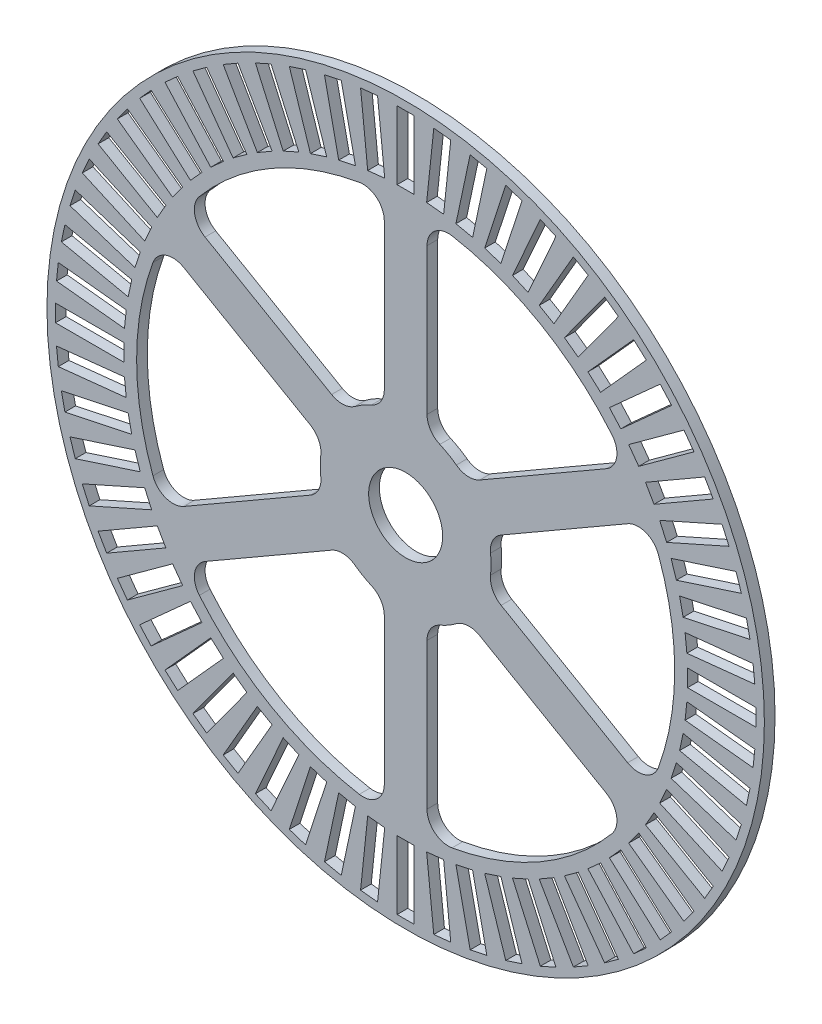
SolidWorks part; units mm, degrees
material "1023 Carbon Steel Sheet (SS)"
ref_plane "Front Plane" through (0, 0, 0) normal (0, 0, 1) x (1, 0, 0)
ref_plane "Top Plane" through (0, 0, 0) normal (0, 1, 0) x (1, 0, 0)
ref_plane "Right Plane" through (0, 0, 0) normal (1, 0, 0) x (0, 0, -1)
sketch "Sketch1" plane through (0, 0, 0) normal (0, 0, 1) x (1, 0, 0)
  circle A0 centre (0, 0) radius 40.005
  circle A1 centre (0, 0) radius 53.34
  dimension "D1" = 106.68
  dimension "D2" = 13.335
extrude "Boss-Extrude1" add sketch "Sketch1" along normal blind 1.5875
sketch "Sketch4" plane through (0, 0, 1.5875) normal (0, 0, 1) x (1, 0, 0)
  line L1 (-1.27, 52.07) -> (1.27, 52.07)
  line L2 (-1.27, 52.07) -> (-1.27, 41.91)
  line L3 (-1.27, 41.91) -> (1.27, 41.91)
  line L4 (1.27, 52.07) -> (1.27, 41.91)
  line L5 (-1.27, 52.07) -> (1.27, 41.91) construction
  line L6 (-1.27, 41.91) -> (1.27, 52.07) construction
  point P0 (0, 46.99)
  dimension "D1" = 2.54
  dimension "D2" = 10.16
  dimension "D3" = 46.99
extrude "Cut-Extrude3" cut sketch "Sketch4" against normal blind 5.08 contours L1 L4 L3 L2
pattern_circular "CirPattern2" count 60 over 360 of "Cut-Extrude3"
sketch "Sketch7" plane through (0, 0, 0) normal (0, 0, -1) x (-1, 0, 0)
  line L0 (-1.905, 0) -> (49998.095, 0) construction
  circle A2 centre (60.325, 0) radius 6.985
  point P6 (60.325, 0)
  dimension "D1" = 60.325
  dimension "D2" = 13.97
extrude "Cut-Extrude5" [suppressed] cut sketch "Sketch7" against normal blind 2.54
pattern_circular "CirPattern4" [suppressed] count 6 over 360 of bodies 110
sketch "Sketch8" plane through (0, 0, 0) normal (0, 0, 1) x (1, 0, 0)
  line L0 (-3.175, 12.2967) -> (-3.175, 39.8788)
  line L1 (3.175, 12.2967) -> (3.175, 39.8788)
  line L2 (9.0618, 8.898) -> (32.9486, 22.689)
  line L3 (12.2368, 3.3987) -> (36.1236, 17.1898)
  line L4 (12.2368, -3.3987) -> (36.1236, -17.1898)
  line L5 (9.0618, -8.898) -> (32.9486, -22.689)
  line L6 (3.175, -12.2967) -> (3.175, -39.8788)
  line L7 (-3.175, -12.2967) -> (-3.175, -39.8788)
  line L8 (-9.0618, -8.898) -> (-32.9486, -22.689)
  line L9 (-12.2368, -3.3987) -> (-36.1236, -17.1898)
  line L10 (-12.2368, 3.3987) -> (-36.1236, 17.1898)
  line L11 (-9.0618, 8.898) -> (-32.9486, 22.689)
  circle A1 centre (0, 0) radius 40.005 construction
  arc A2 (-32.9486, 22.689) -> (-36.1236, 17.1898) centre (0, 0) ccw
  arc A3 (-36.1236, -17.1898) -> (-32.9486, -22.689) centre (0, 0) ccw
  arc A4 (-3.175, -39.8788) -> (3.175, -39.8788) centre (0, 0) ccw
  arc A5 (32.9486, -22.689) -> (36.1236, -17.1898) centre (0, 0) ccw
  arc A6 (36.1236, 17.1898) -> (32.9486, 22.689) centre (0, 0) ccw
  arc A7 (3.175, 39.8788) -> (-3.175, 39.8788) centre (0, 0) ccw
  circle A8 centre (0, 0) radius 5.5
  arc A9 (-12.2368, 3.3987) -> (-12.2368, -3.3987) centre (0, 0) ccw
  arc A10 (-3.175, 12.2967) -> (-9.0618, 8.898) centre (0, 0) ccw
  arc A11 (9.0618, 8.898) -> (3.175, 12.2967) centre (0, 0) ccw
  arc A12 (12.2368, -3.3987) -> (12.2368, 3.3987) centre (0, 0) ccw
  arc A13 (3.175, -12.2967) -> (9.0618, -8.898) centre (0, 0) ccw
  arc A14 (-9.0618, -8.898) -> (-3.175, -12.2967) centre (0, 0) ccw
  point P32 (0, 0)
  dimension "D1" = 11
  dimension "D4" = 25.4
  dimension "D2" = 6.35
  dimension "D3" = 6
extrude "Boss-Extrude2" add sketch "Sketch8" along normal blind 1.5875
fillet "Fillet1" radius 3.175 24 edges at (12.2368, -3.3987, 0.7937) (12.2368, 3.3987, 0.7937) (9.0618, -8.898, 0.7937) (3.175, -12.2967, 0.7937) (-3.175, -12.2967, 0.7937) (-9.0618, -8.898, 0.7937) (-12.2368, 3.3987, 0.7937) (-12.2368, -3.3987, 0.7937) (-3.175, 12.2967, 0.7937) (-9.0618, 8.898, 0.7937) (3.175, 12.2967, 0.7937) (9.0618, 8.898, 0.7937) (3.175, 39.8788, 0.7937) (32.9486, 22.689, 0.7937) (36.1236, 17.1898, 0.7937) (36.1236, -17.1898, 0.7937) (32.9486, -22.689, 0.7937) (3.175, -39.8788, 0.7937) (-3.175, -39.8788, 0.7937) (-32.9486, -22.689, 0.7937) (-36.1236, -17.1898, 0.7937) (-36.1236, 17.1898, 0.7937) (-32.9486, 22.689, 0.7937) (-3.175, 39.8788, 0.7937)
